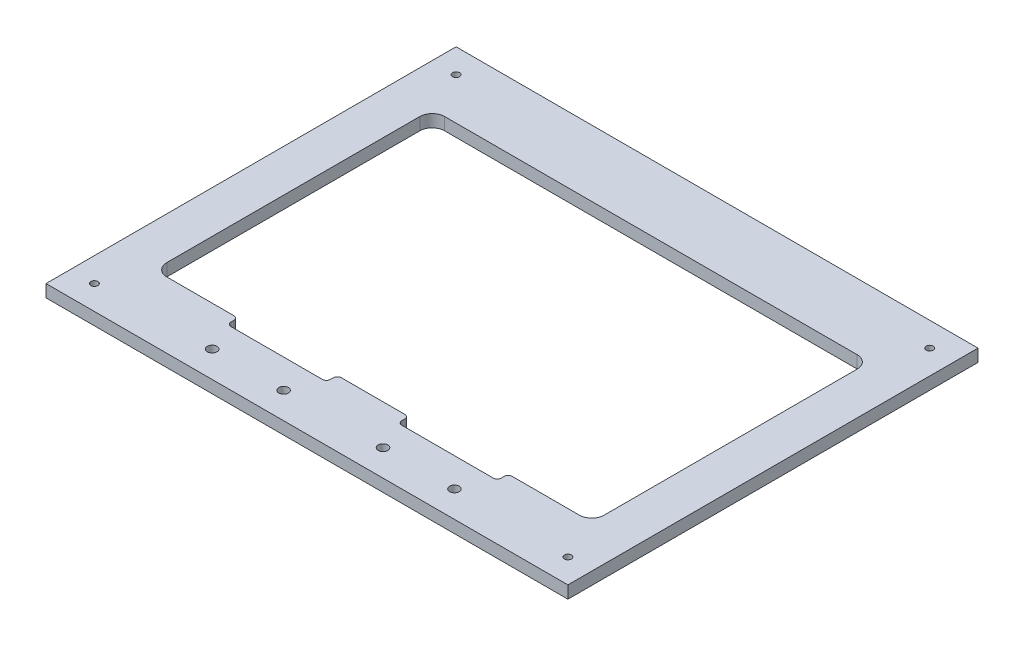
SolidWorks part; units mm, degrees
material "Acrylic (Medium-high impact)"
ref_plane "Front Plane" through (0, 0, 0) normal (0, 0, 1) x (1, 0, 0)
ref_plane "Top Plane" through (0, 0, 0) normal (0, 1, 0) x (1, 0, 0)
ref_plane "Right Plane" through (0, 0, 0) normal (1, 0, 0) x (0, 0, -1)
sketch "Sketch1" plane through (0, 0, 0) normal (0, 1, 0) x (1, 0, 0)
  line L1 (-133.35, 104.775) -> (133.35, 104.775)
  line L2 (-133.35, 104.775) -> (-133.35, -104.775)
  line L3 (-133.35, -104.775) -> (133.35, -104.775)
  line L4 (133.35, 104.775) -> (133.35, -104.775)
  line L5 (-133.35, 104.775) -> (133.35, -104.775) construction
  line L6 (-133.35, -104.775) -> (133.35, 104.775) construction
  point P0 (0, 0)
  dimension "D1" = 209.55
  dimension "D2" = 266.7
extrude "Boss-Extrude1" add sketch "Sketch1" along normal blind 6.35
hole_wizard "M3 Clearance Hole1" positions "Sketch2" profile "Sketch3" hole size "M3" standard "ANSI Metric" end condition through all
sketch "Sketch2" plane through (0, 6.35, 0) normal (0, 1, 0) x (1, 0, 0)
  line L0 (-133.35, -104.775) -> (133.35, -104.775) construction
  line L1 (133.35, -104.775) -> (133.35, 104.775) construction
  line L2 (133.35, 104.775) -> (-133.35, 104.775) construction
  line L3 (-133.35, 104.775) -> (-133.35, -104.775) construction
  point P0 (121.0056, -92.4306)
  point P2 (-121.0056, -92.4306)
  point P4 (-121.0056, 92.4306)
  point P6 (121.0056, 92.4306)
  dimension "D1" = 12.3444
  dimension "D2" = 12.3444
  dimension "D3" = 12.3444
  dimension "D4" = 12.3444
sketch "Sketch3" plane through (121.0056, 6.35, 92.4306) normal (1, 0, 0) x (0, 0, 1)
  line L0 (0, 0) -> (0, 6.35)
  line L1 (0, 6.35) -> (1.8, 6.35)
  line L2 (1.8, 6.35) -> (1.8, 0)
  line L5 (1.8, 0) -> (0, 0)
  line L11 (0, -6.35) -> (0, 107.95) construction
  dimension "Thru Hole Dia." = 3.6
  dimension "Thru Hole Depth" = 6.35
sketch "Sketch4" plane through (0, 6.35, 0) normal (0, 1, 0) x (1, 0, 0)
  line L0 (-133.35, 104.775) -> (-133.35, -104.775) construction
  line L1 (111.76, -70.993) -> (-111.76, -70.993)
  line L2 (111.76, -70.993) -> (111.76, 70.993)
  line L3 (111.76, 70.993) -> (-111.76, 70.993)
  line L4 (-111.76, -70.993) -> (-111.76, 70.993)
  line L5 (111.76, -70.993) -> (-111.76, 70.993) construction
  line L6 (111.76, 70.993) -> (-111.76, -70.993) construction
  line L7 (133.35, 104.775) -> (-133.35, 104.775) construction
  point P0 (0, 0)
  dimension "D1" = 21.59
  dimension "D2" = 33.782
extrude "Cut-Extrude1" cut sketch "Sketch4" against normal through all
hole_wizard "#8 Clearance Hole1" positions "Sketch5" profile "Sketch6" hole size "#8" standard "ANSI Inch" end condition through all
sketch "Sketch5" plane through (0, 6.35, 0) normal (0, 1, 0) x (1, 0, 0)
  line L0 (-61.9125, -91.313) -> (-25.4, -91.313) construction
  line L2 (25.4, -91.313) -> (61.9125, -91.313) construction
  line L4 (-25.4, -91.313) -> (25.4, -91.313) construction
  line L5 (-111.76, -70.993) -> (111.76, -70.993) construction
  point P0 (-61.9125, -91.313)
  point P4 (-25.4, -91.313)
  point P6 (25.4, -91.313)
  point P10 (61.9125, -91.313)
  point P29 (0, -91.313)
  dimension "D1" = 36.5125
  dimension "D2" = 36.5125
  dimension "D3" = 50.8
  dimension "D4" = 20.32
sketch "Sketch6" plane through (-61.9125, 6.35, 91.313) normal (1, 0, 0) x (0, 0, 1)
  line L0 (0, 0) -> (0, 6.35)
  line L1 (0, 6.35) -> (2.4574, 6.35)
  line L2 (2.4574, 6.35) -> (2.4574, 0)
  line L5 (2.4574, 0) -> (0, 0)
  line L11 (0, -6.35) -> (0, 107.95) construction
  dimension "Thru Hole Dia." = 4.9149
  dimension "Thru Hole Depth" = 6.35
sketch "Sketch7" plane through (0, 6.35, 0) normal (0, 1, 0) x (1, 0, 0)
  line L0 (-111.76, -70.993) -> (111.76, -70.993) construction
  line L1 (-69.0563, -76.581) -> (-18.2563, -76.581)
  line L2 (-69.0563, -76.581) -> (-69.0563, -70.993)
  line L3 (-69.0563, -70.993) -> (-18.2563, -70.993)
  line L4 (-18.2563, -76.581) -> (-18.2563, -70.993)
  line L5 (-69.0563, -76.581) -> (-18.2563, -70.993) construction
  line L6 (-69.0563, -70.993) -> (-18.2563, -76.581) construction
  line L7 (-43.6562, -73.787) -> (-43.6562, -91.313) construction
  line L8 (18.2562, -76.581) -> (69.0562, -76.581)
  line L9 (18.2562, -76.581) -> (18.2562, -70.993)
  line L10 (18.2562, -70.993) -> (69.0562, -70.993)
  line L11 (69.0562, -76.581) -> (69.0562, -70.993)
  line L12 (18.2562, -76.581) -> (69.0562, -70.993) construction
  line L13 (18.2562, -70.993) -> (69.0562, -76.581) construction
  line L14 (43.6562, -73.787) -> (43.6562, -91.313) construction
  line L15 (-61.9125, -91.313) -> (-25.4, -91.313) construction
  line L16 (25.4, -91.313) -> (61.9125, -91.313) construction
  point P0 (-43.6563, -73.787)
  point P7 (43.6562, -73.787)
  dimension "D3" = 50.8
  dimension "D4" = 5.588
extrude "Cut-Extrude2" cut sketch "Sketch7" against normal through all
fillet "Fillet1" radius 6.35 4 edges at (111.76, 3.175, -70.993) (111.76, 3.175, 70.993) (-111.76, 3.175, 70.993) (-111.76, 3.175, -70.993)
fillet "Fillet2" radius 2.032 8 edges at (69.0562, 3.175, 70.993) (69.0562, 3.175, 76.581) (18.2562, 3.175, 76.581) (18.2562, 3.175, 70.993) (-18.2563, 3.175, 70.993) (-18.2563, 3.175, 76.581) (-69.0562, 3.175, 70.993) (-69.0563, 3.175, 76.581)
